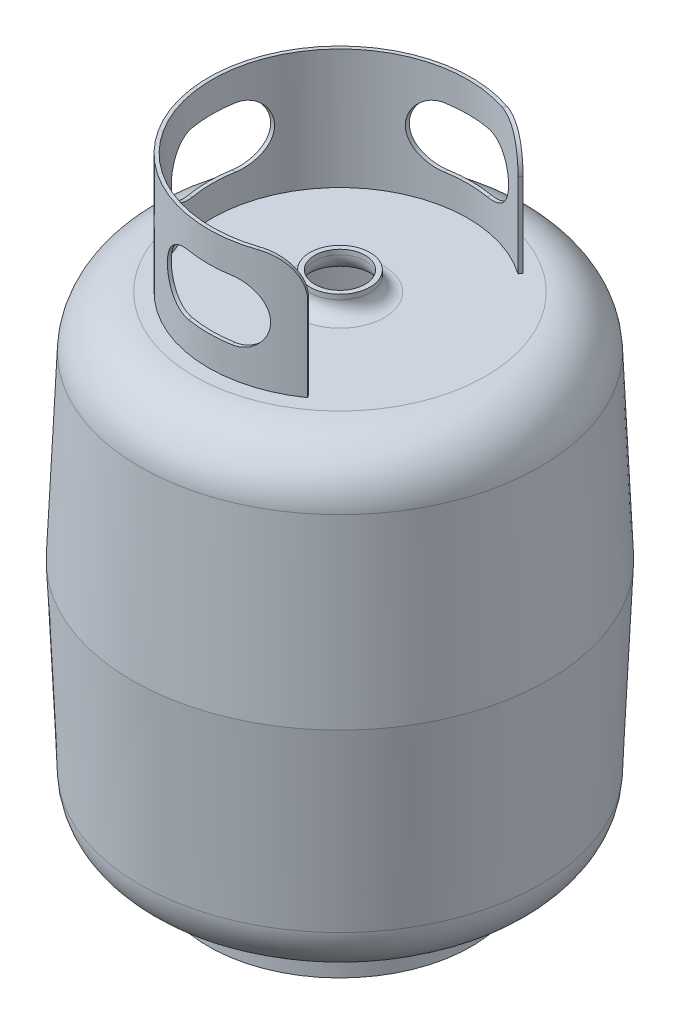
SolidWorks part; units mm, degrees
material "1060 Alloy"
ref_plane "Front Plane" through (0, 0, 0) normal (0, 0, 1) x (1, 0, 0)
ref_plane "Top Plane" through (0, 0, 0) normal (0, 1, 0) x (1, 0, 0)
ref_plane "Right Plane" through (0, 0, 0) normal (1, 0, 0) x (0, 0, -1)
sketch "Sketch1" plane through (0, 0, 0) normal (0, 0, 1) x (1, 0, 0)
  line L0 (0, 284.3118) -> (0, -284.3118) construction
  line L1 (-297.809, 0) -> (297.809, 0) construction
  line L2 (0, -193.75) -> (-121.539, -193.75)
  line L3 (-166.4962, -150.7129) -> (-173.0765, 0)
  line L4 (-173.0765, 0) -> (-166.4962, 150.7129)
  line L5 (-121.539, 193.75) -> (-37, 193.75)
  line L6 (-25, 205.75) -> (-25, 209.75)
  line L7 (0, -189.75) -> (-121.539, -189.75)
  line L8 (-162.5, -150.5384) -> (-169.0726, 0)
  line L9 (-169.0726, 0) -> (-162.5, 150.5384)
  line L10 (-121.539, 189.75) -> (-37, 189.75)
  line L11 (-21, 205.75) -> (-21, 209.75)
  line L12 (-25, 209.75) -> (-21, 209.75)
  line L13 (0, -189.75) -> (0, -193.75)
  line L14 (-162.5, 150.5384) -> (-162.5, 191.7014) construction
  arc A0 (-37, 193.75) -> (-25, 205.75) centre (-37, 205.75) ccw
  arc A1 (-121.539, -193.75) -> (-166.4962, -150.7129) centre (-121.539, -148.75) cw
  arc A2 (-166.4962, 150.7129) -> (-121.539, 193.75) centre (-121.539, 148.75) cw
  arc A3 (-121.539, -189.75) -> (-162.5, -150.5384) centre (-121.539, -148.75) cw
  arc A4 (-162.5, 150.5384) -> (-121.539, 189.75) centre (-121.539, 148.75) cw
  arc A5 (-37, 189.75) -> (-21, 205.75) centre (-37, 205.75) ccw
  point P4 (0, 0)
  point P8 (0, 0)
  dimension "D5" = 12
  dimension "D6" = 45
  dimension "D1" = 387.5
  dimension "D2" = 92.5
  dimension "D3" = 92.5
  dimension "D4" = 50
  dimension "D8" = 20
  dimension "D9" = 325
  dimension "D7" = 4
revolve "Revolve2" add sketch "Sketch1" angle 360 about L0
sketch "Sketch2" plane through (0, -193.75, 0) normal (0, -1, 0) x (1, 0, 0)
  circle A0 centre (0, 0) radius 109.539
  circle A1 centre (0, 0) radius 121.539 construction
  circle A2 centre (0, 0) radius 106.539
  dimension "D1" = 12
  dimension "D2" = 3
extrude "Boss-Extrude1" add sketch "Sketch2" along normal blind 30
sketch "Sketch3" plane through (0, 193.75, 0) normal (0, 1, 0) x (1, 0, 0)
  line L0 (69.7119, 99.5589) -> (0, 0) construction
  line L1 (0, 0) -> (121.539, 0) construction
  line L2 (69.7119, -99.5589) -> (0, 0) construction
  line L3 (62.829, 89.7291) -> (61.1083, 87.2717)
  line L4 (61.1083, -87.2717) -> (62.829, -89.7291)
  arc A0 (62.829, 89.7291) -> (62.829, -89.7291) centre (0, 0) ccw
  circle A1 centre (0, 0) radius 121.539 construction
  arc A2 (61.1083, 87.2717) -> (61.1083, -87.2717) centre (0, 0) ccw
  circle A3 centre (0, 0) radius 106.539 construction
  circle A4 centre (0, 0) radius 109.539 construction
  dimension "D1" = 12
  dimension "D3" = 55
  dimension "D2" = 3
extrude "Boss-Extrude2" add sketch "Sketch3" along normal blind 100
sketch "Sketch4" plane through (0, 0, 0) normal (0, 0, 1) x (1, 0, 0)
  line L0 (0, 0) -> (0, 293.75) construction
  line L1 (61.1083, 293.75) -> (-106.539, 293.75) construction
  line L2 (-18, 243.75) -> (18, 243.75) construction
  line L3 (-18, 268.75) -> (18, 268.75)
  line L4 (-18, 218.75) -> (18, 218.75)
  arc A0 (-18, 268.75) -> (-18, 218.75) centre (-18, 243.75) ccw
  arc A1 (18, 218.75) -> (18, 268.75) centre (18, 243.75) ccw
  point P7 (0, 243.75)
  point P12 (0, 0)
  point P13 (0, 0)
  dimension "D1" = 50
  dimension "D2" = 50
  dimension "D3" = 18
extrude "Cut-Extrude4" cut sketch "Sketch4" against normal through all
pattern_circular "CirPattern3" count 3 over 180 about axis through (0, 293.75, 0) along (0, -1, 0) of "Cut-Extrude4" reverse direction yes
fillet "Fillet1" radius 30 2 edges at (61.9686, 293.75, 88.5004) (61.9686, 293.75, -88.5004)
equation "\"A\"= 325mm"
equation "\"B\"= 387.5mm"
equation "\"D1@Sketch1\"=\"B\""
equation "\"D9@Sketch1\"=\"A\""
